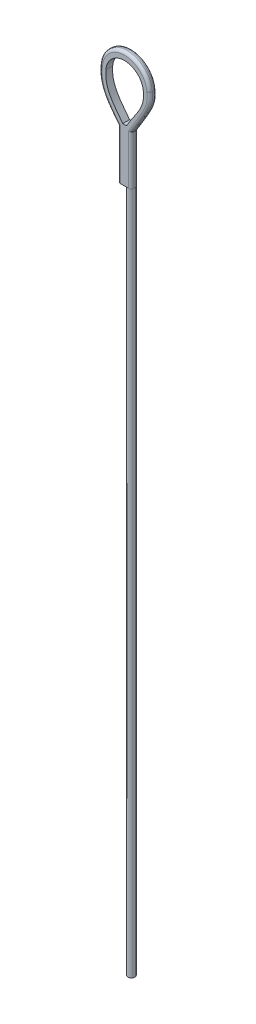
SolidWorks part; units mm, degrees
note: '?' marks a value the reader was unsure of.
ref_plane "Front Plane" through (0, 0, 0) normal (0, 0, 1) x (1, 0, 0)
ref_plane "Top Plane" through (0, 0, 0) normal (0, 1, 0) x (1, 0, 0)
ref_plane "Right Plane" through (0, 0, 0) normal (1, 0, 0) x (0, 0, -1)
sketch "Sketch1" plane through (0, 0, 0) normal (0, 1, 0) x (1, 0, 0)
  circle A0 centre (0, 0) radius 0.635
  dimension "D1" = 1.27
extrude "Boss-Extrude1" add sketch "Sketch1" along normal blind 127
ref_axis "Axis1" through (0, 127, 0) along (0, -1, 0)?
ref_point "Point1"
sketch "Sketch2" plane through (0, 0, 0) normal (0, 0, 1) x (1, 0, 0)
  line L0 (0.635, 127) -> (0.635, 136.1584)
  line L2 (0.635, 0) -> (0.635, 127) construction
  line L4 (0.635, 41.6416) -> (0.635, 136.1584)
  line L5 (-1.905, 127) -> (0.635, 127)
  line L6 (-1.905, 127) -> (-1.905, 136.1584)
  line L7 (0.635, 0) -> (0.635, 136.1584)
  line L8 (-0.2972, 136.8802) -> (-0.9728, 136.8802)
  arc A1 (2.8449, 143.9954) -> (-4.1149, 143.9954) centre (-0.635, 143.6988) ccw
  arc A4 (4.0057, 144.3073) -> (-5.2893, 144.0985) centre (-0.635, 143.9) ccw
  spline S0 degree 3 poles (0.635, 136.1584) (4.1536, 141.8188) (4.1147, 141.9921) (4.0057, 144.3073) knots 0 0 0 0 1 1 1 1
  spline S1 degree 3 poles (-1.905, 136.1584) (-3.7183, 138.5004) (-5.5986, 140.574) (-5.2893, 144.0985) knots 0 0 0 0 1 1 1 1
  spline S2 degree 3 poles (-0.2972, 136.8802) (-0.1076, 137.2232) (0.3135, 137.9054) (1.1492, 139.11) (1.9153, 140.2056) (2.4624, 141.2722) (2.7481, 142.0851) (2.871, 142.8169) (2.8885, 143.4581) (2.8643, 143.8205) (2.8449, 143.9954) knots 0 0 0 0 0.125 0.25 0.5 0.625 0.75 0.875 0.9375 1 1 1 1
  spline S5 degree 3 poles (-0.9728, 136.8802) (-1.1986, 137.1719) (-1.6634, 137.761) (-2.5177, 138.8703) (-3.24, 139.9527) (-3.7493, 141.0661) (-4.0163, 141.9421) (-4.1321, 142.7393) (-4.1505, 143.4298) (-4.1311, 143.8103) (-4.1149, 143.9954) knots 0 0 0 0 0.125 0.25 0.5 0.625 0.75 0.875 0.9375 1 1 1 1
  dimension "D2" = 3.4925
  dimension "D3" = 7.9498
extrude "Boss-Extrude2" add sketch "Sketch2" along normal through all and the other way through all contours S1 L6 L5 L4 S0 A4 L8 S5 A1 S2
fillet "Fillet1" radius 0.508 10 edges at (-1.905, 131.5792, -0.635) (0.635, 131.5792, -0.635) (-1.905, 131.5792, 0.635) (0.635, 131.5792, 0.635) (-0.7396, 148.5574, -0.635) (-0.7396, 148.5574, 0.635)
